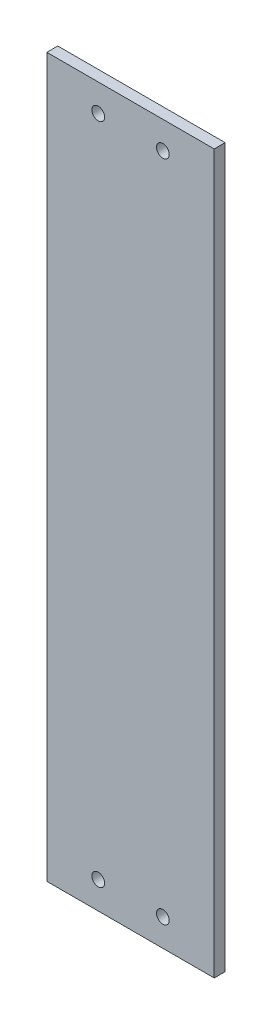
SolidWorks part; units mm, degrees
ref_plane "Front Plane" through (0, 0, 0) normal (0, 0, 1) x (1, 0, 0)
ref_plane "Top Plane" through (0, 0, 0) normal (0, 1, 0) x (1, 0, 0)
ref_plane "Right Plane" through (0, 0, 0) normal (1, 0, 0) x (0, 0, -1)
sketch "Sketch1" plane through (0, 0, 0) normal (0, 0, 1) x (1, 0, 0)
  line L0 (-104.87, -114.014) -> (-80.55, -114.014)
  line L1 (-80.55, -114.014) -> (-80.55, -9.684)
  line L2 (-80.55, -9.684) -> (-104.87, -9.684)
  line L3 (-104.87, -9.684) -> (-104.87, -114.014)
  line L4 (-105.87, -115.014) -> (-79.55, -115.014)
  line L5 (-105.87, -8.684) -> (-105.87, -115.014)
  line L6 (-79.55, -8.684) -> (-105.87, -8.684)
  line L7 (-79.55, -115.014) -> (-79.55, -8.684)
  line L8 (-105.87, -115.014) -> (-79.55, -115.014) construction
  line L9 (-105.87, -8.684) -> (-105.87, -115.014) construction
  line L10 (-79.55, -8.684) -> (-105.87, -8.684) construction
  line L11 (-79.55, -115.014) -> (-79.55, -8.684) construction
  dimension "D1" = 0
  dimension "D2" = 1
extrude "Boss-Extrude1" add sketch "Sketch1" along normal blind 1.5875
hole_wizard "#0 Clearance Hole1" positions "Sketch3" profile "Sketch2" hole size "#0" standard "ANSI Inch" end condition through all
sketch "Sketch3" plane through (0, 0, 1.5875) normal (0, 0, 1) x (1, 0, 0)
  point P0 (-88.011, -110.0455)
  point P3 (-97.409, -110.0455)
  point P7 (-88.011, -13.6525)
  point P10 (-97.409, -13.6525)
sketch "Sketch2" plane through (-88.011, -110.0455, 1.5875) normal (1, 0, 0) x (0, -1, 0)
  line L0 (0, 0) -> (0, 1.5875)
  line L1 (0, 1.5875) -> (0.9271, 1.5875)
  line L2 (0.9271, 1.5875) -> (0.9271, 0)
  line L5 (0.9271, 0) -> (0, 0)
  line L11 (0, -6.35) -> (0, 107.95) construction
  dimension "Thru Hole Dia." = 1.8542
  dimension "Thru Hole Depth" = 1.5875
